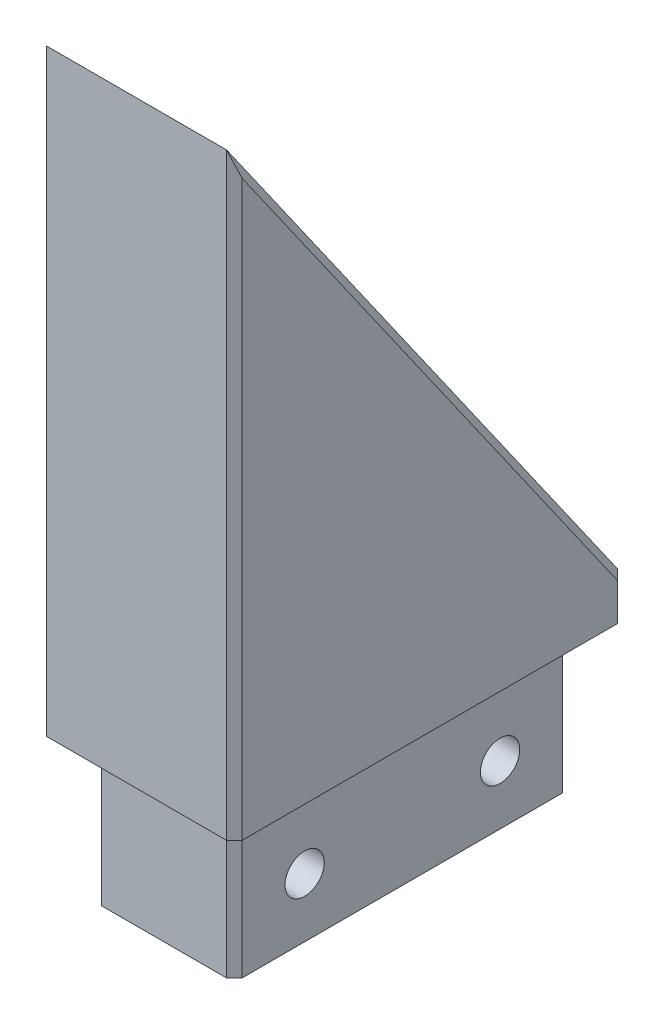
SolidWorks part; units mm, degrees
material "Nylon 101"
ref_plane "Front Plane" through (0, 0, 0) normal (0, 0, 1) x (1, 0, 0)
ref_plane "Top Plane" through (0, 0, 0) normal (0, 1, 0) x (1, 0, 0)
ref_plane "Right Plane" through (0, 0, 0) normal (1, 0, 0) x (0, 0, -1)
sketch "Sketch1" plane through (0, 0, 0) normal (1, 0, 0) x (0, 0, -1)
  line L0 (0, 0) -> (0, 77.724)
  line L1 (0, 77.724) -> (50.8, 5.1741)
  line L2 (50.8, 5.1741) -> (50.8, 0)
  line L3 (50.8, 0) -> (0, 0)
  dimension "D1" = 55
  dimension "D2" = 77.724
  dimension "D3" = 50.8
extrude "Boss-Extrude1" add sketch "Sketch1" along normal mid plane 25.4
sketch "Sketch2" plane through (0, 0, 0) normal (0, -1, 0) x (1, 0, 0)
  line L0 (0, -47.244) -> (0, -50.8) construction
  line L1 (9.144, -3.556) -> (-9.144, -3.556)
  line L2 (9.144, -3.556) -> (9.144, -47.244)
  line L3 (9.144, -47.244) -> (-9.144, -47.244)
  line L4 (-9.144, -3.556) -> (-9.144, -47.244)
  line L5 (12.7, -50.8) -> (-12.7, -50.8) construction
  line L6 (9.144, -25.4) -> (12.7, -25.4) construction
  line L7 (12.7, 0) -> (12.7, -50.8) construction
  dimension "D1" = 43.688
  dimension "D2" = 18.288
  dimension "D3" = 3.556
extrude "Boss-Extrude2" add sketch "Sketch2" along normal blind 19.05
sketch "Sketch3" plane through (9.144, 0, 0) normal (1, 0, 0) x (0, 0, -1)
  line L0 (3.556, -11.3754) -> (47.244, -11.3754) construction
  line L4 (3.556, -19.05) -> (3.556, 0) construction
  line L5 (47.244, -19.05) -> (47.244, 0) construction
  circle A1 centre (38.1, -11.3754) radius 2.5527
  circle A2 centre (12.7, -11.3754) radius 2.5527
  point P2 (3.556, -11.3754)
  point P5 (47.244, -11.3754)
  point P6 (12.7, -11.3754)
  point P7 (0, 0)
  dimension "D2" = 9.144
  dimension "D4" = 5.1054
  dimension "D1" = 25.4
extrude "Cut-Extrude1" cut sketch "Sketch3" against normal through all
chamfer "Chamfer1" distance 1 angle 45 10 edges at (-9.144, -9.525, -3.556) (9.144, -9.525, -3.556) (-9.144, -9.525, -47.244) (9.144, -9.525, -47.244) (-12.7, 2.587, -50.8) (-12.7, 41.449, -25.4) (-12.7, 38.862, 0) (12.7, 2.587, -50.8) (12.7, 41.449, -25.4) (12.7, 38.862, 0)
